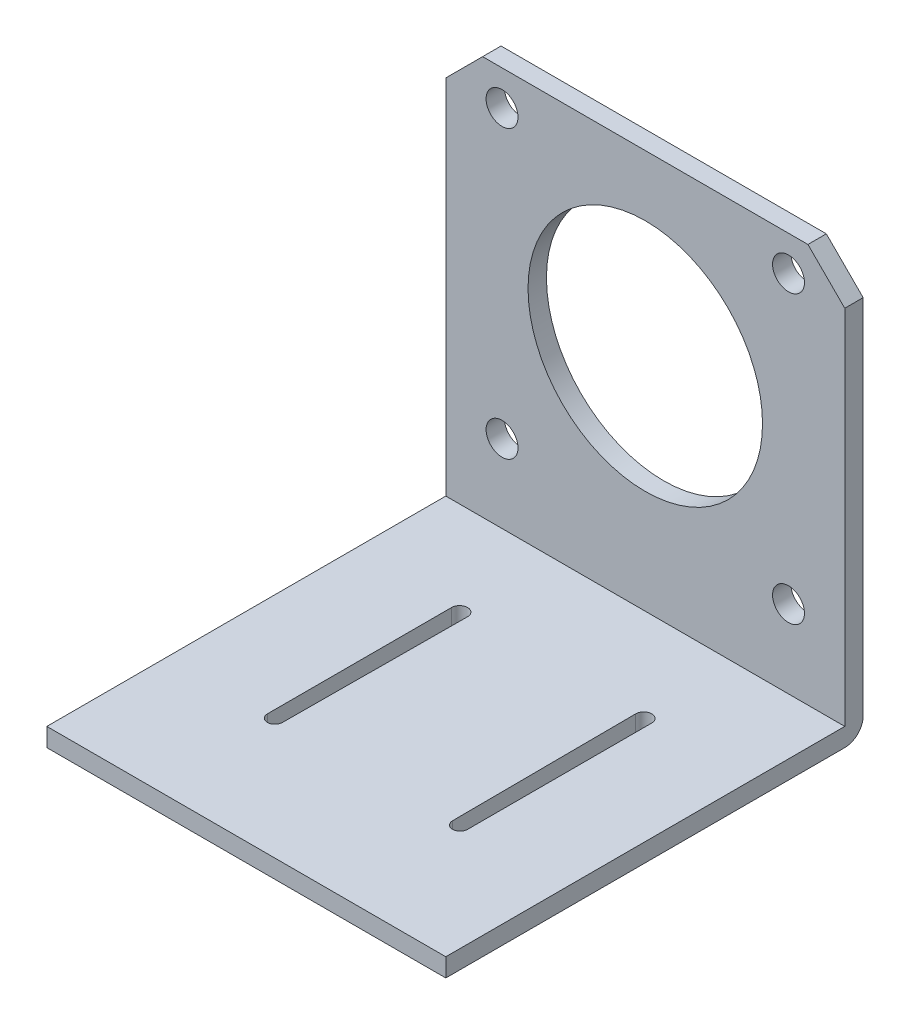
SolidWorks part; units mm, degrees
material "Серое литое железо"
ref_plane "Спереди" through (0, 0, 0) normal (0, 0, 1) x (1, 0, 0)
ref_plane "Сверху" through (0, 0, 0) normal (0, 1, 0) x (1, 0, 0)
ref_plane "Справа" through (0, 0, 0) normal (1, 0, 0) x (0, 0, -1)
sketch "Эскиз1" plane through (0, 0, 0) normal (1, 0, 0) x (0, 0, -1)
  line L3 (7, 65) -> (7, -3)
  line L4 (7, -3) -> (-61, -3)
  line L5 (-61, -3) -> (-61, 0)
  line L6 (7, 65) -> (4, 65)
  line L7 (4, 65) -> (4, 0)
  line L8 (4, 0) -> (-61, 0)
  dimension "D1" = 68
  dimension "D2" = 68
  dimension "D3" = 3
  dimension "D4" = 3
extrude "Бобышка-Вытянуть1" add sketch "Эскиз1" along normal blind 32.5 and the other way blind 32.5
fillet "Скругление2" radius 3 1 edges at (0, -3, -7)
sketch "Эскиз2" plane through (0, 0, -7) normal (0, 0, -1) x (-1, 0, 0)
  line L0 (32.5, 65) -> (-32.5, 65) construction
  line L1 (25.25, 46) -> (-25.25, 46) construction
  line L2 (0, 36) -> (-14.5371, 50.5371) construction
  line L3 (0, 36) -> (-23.1365, 36) construction
  line L4 (-26.5, 65) -> (-32.5, 59)
  line L5 (-32.5, 59) -> (-32.5, 65)
  line L6 (-32.5, 65) -> (-26.5, 65)
  line L7 (32.5, 59) -> (32.5, 65)
  line L8 (26.5, 65) -> (32.5, 59)
  line L9 (0, 46) -> (0, 6.4441) construction
  line L10 (32.5, 65) -> (26.5, 65)
  circle A0 centre (0, 36) radius 19.1
  circle A4 centre (-23.3345, 59.3345) radius 2.6
  circle A11 centre (23.3345, 59.3345) radius 2.6
  circle A12 centre (23.3345, 12.6655) radius 2.6
  circle A13 centre (-23.3345, 12.6655) radius 2.6
  point P22 (0, 36)
  point P28 (0, 25.5)
  dimension "D2" = 38.2
  dimension "D3" = 45
  dimension "D4" = 33
  dimension "D5" = 5.2
  dimension "D1" = 29
  dimension "D6" = 4
extrude "Вырез-Вытянуть1" cut sketch "Эскиз2" against normal blind 13.125
sketch "Эскиз3" plane through (0, 0, 0) normal (0, 1, 0) x (1, 0, 0)
  line L0 (0, -4.9378) -> (0, -56.3475) construction
  line L1 (-16.3045, -11.2536) -> (-16.3045, -41.2536)
  line L2 (-13.6955, -11.2536) -> (-13.8626, -41.2536)
  line L3 (16.3045, -11.2536) -> (16.3045, -41.2536)
  line L4 (13.6955, -11.2536) -> (13.8626, -41.2536)
  arc A0 (-13.6955, -11.2681) -> (-16.3045, -11.2536) centre (-15, -11.2536) ccw
  arc A1 (-16.3045, -41.2536) -> (-13.8626, -41.2536) centre (-15.0836, -41.2536) ccw
  arc A2 (16.3045, -41.2536) -> (13.8626, -41.2536) centre (15.0836, -41.2536) cw
  arc A3 (13.6955, -11.2681) -> (16.3045, -11.2536) centre (15, -11.2536) cw
  dimension "D1" = 30
  dimension "D2" = 15
extrude "Вырез-Вытянуть2" cut sketch "Эскиз3" against normal blind 10 contours L1 A1 L2 A0 | A3 L4 A2 L3 region at (-15.0412, 0, 26.0335) region at (15.0412, 0, 26.0335)
